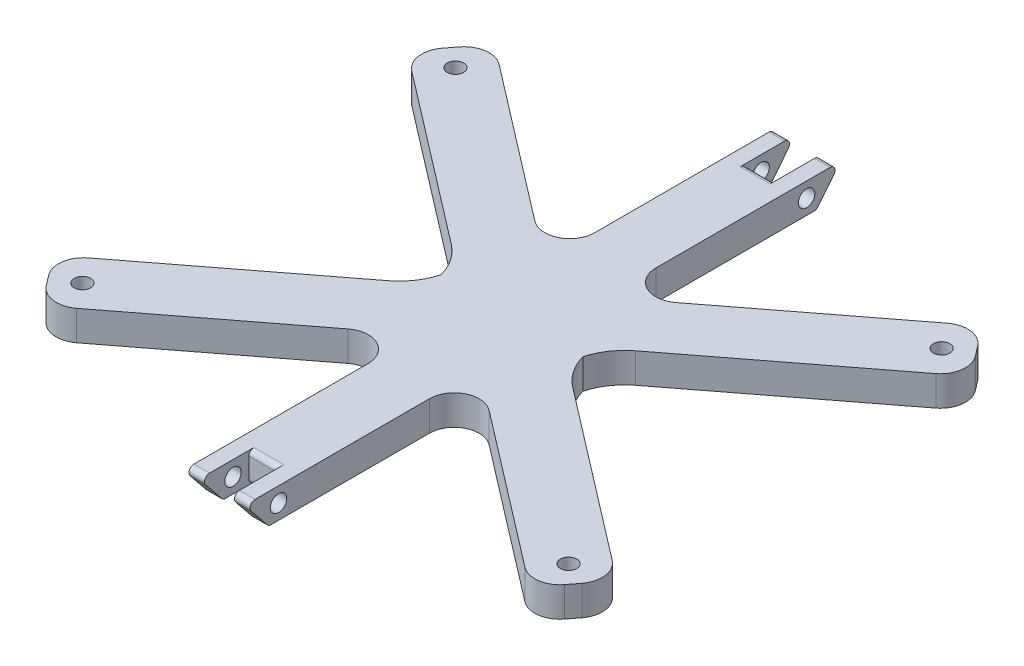
SolidWorks part; units mm, degrees
ref_plane "Front Plane" through (0, 0, 0) normal (0, 0, 1) x (1, 0, 0)
ref_plane "Top Plane" through (0, 0, 0) normal (0, 1, 0) x (1, 0, 0)
ref_plane "Right Plane" through (0, 0, 0) normal (1, 0, 0) x (0, 0, -1)
sketch "Sketch1" plane through (0, 0, 0) normal (0, 1, 0) x (1, 0, 0)
  circle A0 centre (0, 0) radius 14
  dimension "D1" = 28
extrude "Boss-Extrude1" add sketch "Sketch1" along normal blind 6
sketch "Sketch2" plane through (0, 0, 0) normal (0, 1, 0) x (1, 0, 0)
  line L0 (-13.7435, 2.6678) -> (-56.5628, 35.5242)
  line L1 (0.2695, -0.2068) -> (-63.7589, 48.924) construction
  line L2 (-48.9532, 45.4411) -> (-6.134, 12.5847)
  line L3 (0, 37.6664) -> (0, -25.0328) construction
  line L4 (-48.9532, 45.4411) -> (-56.5628, 35.5242)
  circle A0 centre (0, 0) radius 14 construction
  arc A1 (-6.134, 12.5847) -> (-13.7435, 2.6678) centre (0, 0) ccw
  point P9 (-52.758, 40.4826)
  dimension "D1" = 66.5
  dimension "D2" = 52.5
  dimension "D3" = 12.5
extrude "Boss-Extrude2" add sketch "Sketch2" along normal up to surface (6 mm away) up to face at (0, 6, 14)
mirror "Mirror1" about plane through (0, 0, 0) normal (1, 0, 0) of "Boss-Extrude2"
mirror "Mirror2" about plane through (0, 0, 0) normal (0, 0, 1) of "Mirror1", "Boss-Extrude2"
sketch "Sketch4" plane through (0, 6, 0) normal (0, 1, 0) x (1, 0, 0)
  line L0 (0, 65.599) -> (0, -44.8835) construction
  line L1 (-6.134, 59.8) -> (-6.134, 12.5847)
  line L2 (-6.134, 59.8) -> (6.134, 59.8)
  line L3 (6.134, 59.8) -> (6.134, 12.5847)
  arc A2 (6.134, 12.5847) -> (-6.134, 12.5847) centre (0, 0) ccw construction
  arc A3 (6.134, 12.5847) -> (-6.134, 12.5847) centre (0, 0) ccw
  point P8 (0, 59.8)
  dimension "D2" = 59.8
extrude "Boss-Extrude4" add sketch "Sketch4" against normal up to surface (6 mm away) up to face at (0, 0, 0)
mirror "Mirror6" about plane through (0, 0, 0) normal (0, 0, 1) of "Boss-Extrude4"
fillet "Fillet4" radius 5 4 edges at (6.134, 3, 12.5847) (-6.134, 3, 12.5847) (6.134, 3, -12.5847) (-6.134, 3, -12.5847)
fillet "Fillet5" radius 12 4 edges at (-13.7435, 3, 2.6678) (-13.7435, 3, -2.6678) (13.7435, 3, 2.6678) (13.7435, 3, -2.6678)
sketch "Sketch3" plane through (0, 6, 0) normal (0, 1, 0) x (1, 0, 0)
  line L1 (-48.9532, 45.4411) -> (-56.5628, 35.5242) construction
  circle A0 centre (-48.7912, 37.4388) radius 1.65
  point P7 (-52.758, 40.4826)
  dimension "D1" = 3.3
  dimension "D2" = 61.5
extrude "Cut-Extrude1" cut sketch "Sketch3" against normal through all
mirror "Mirror3" about plane through (0, 0, 0) normal (1, 0, 0) of "Cut-Extrude1"
mirror "Mirror4" about plane through (0, 0, 0) normal (0, 0, 1) of "Mirror3", "Cut-Extrude1"
sketch "Sketch5" plane through (0, 6, 0) normal (0, 1, 0) x (1, 0, 0)
  line L0 (6.134, 59.8) -> (-6.134, 59.8) construction
  circle A0 centre (0, 54.8) radius 1.65
  dimension "D1" = 3.3
  dimension "D2" = 5
extrude "Cut-Extrude2" [suppressed] cut sketch "Sketch5" against normal through all
mirror "Mirror7" [suppressed] about plane through (0, 0, 0) normal (0, 0, 1)
fillet "Fillet3" radius 5 8 edges at (48.9532, 3, 45.4411) (56.5628, 3, 35.5242) (56.5628, 3, -35.5242) (48.9532, 3, -45.4411) (-48.9532, 3, -45.4411) (-56.5628, 3, -35.5242) (-56.5628, 3, 35.5242) (-48.9532, 3, 45.4411)
sketch "Sketch12" plane through (-6.134, 0, 0) normal (-1, 0, 0) x (0, 0, 1)
  line L0 (-59.8, 6) -> (-54.981, 0)
  line L1 (-22.7237, 0) -> (-59.8, 0) construction
  line L2 (-54.981, 0) -> (-59.8, 0)
  line L3 (-59.8, 0) -> (-59.8, 6)
  dimension "D1" = 128.77
extrude "Cut-Extrude8" cut sketch "Sketch12" against normal blind 14
sketch "Sketch13" plane through (-6.134, 0, 0) normal (-1, 0, 0) x (0, 0, 1)
  circle A0 centre (-53, 3) radius 1.65
  dimension "D2" = 3.3
  dimension "D1" = 53
extrude "Cut-Extrude9" cut sketch "Sketch13" against normal blind 14
sketch "Sketch14" plane through (0, 6, 0) normal (0, 1, 0) x (1, 0, 0)
  line L0 (-3, 59.8) -> (3, 59.8)
  line L1 (6.134, 59.8) -> (-6.134, 59.8) construction
  line L2 (3, 59.8) -> (3, 49.8)
  line L3 (3, 49.8) -> (-3, 49.8)
  line L4 (-3, 49.8) -> (-3, 59.8)
  point P4 (0, 49.8)
  dimension "D1" = 10
  dimension "D2" = 6
extrude "Cut-Extrude10" cut sketch "Sketch14" against normal blind 14
fillet "Fillet6" radius 1 6 edges at (-4.567, 6, -59.8) (4.567, 6, -59.8) (-4.567, 0, -54.981) (4.567, 0, -54.981) (0, 0, -49.8) (0, 6, -49.8)
mirror "Mirror8" about plane through (0, 0, 0) normal (0, 0, 1) of "Fillet6", "Cut-Extrude10", "Cut-Extrude9", "Cut-Extrude8"
